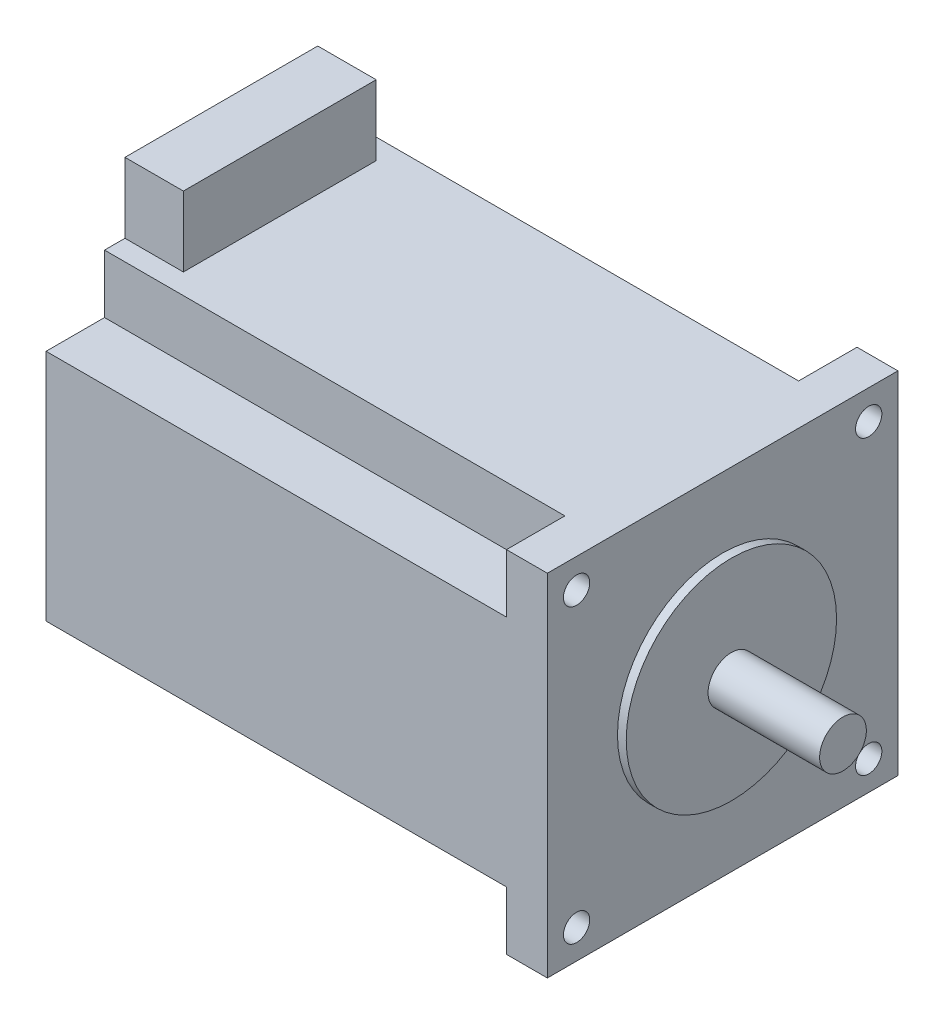
SolidWorks part; units mm, degrees
note: The reader was unsure of these and kept them because the rebuilt part matched: shared geometry of "Sketch1<5>", "Sketch2<2>".
material "7079 Alloy"
ref_plane "Front" through (0, 0, 0) normal (0, 0, 1) x (1, 0, 0)
ref_plane "Top" through (0, 0, 0) normal (0, 1, 0) x (1, 0, 0)
ref_plane "Right" through (0, 0, 0) normal (1, 0, 0) x (0, 0, -1)
sketch "Sketch1" plane through (0, 0, 0) normal (0, 0, 1) x (1, 0, 0)
  line L0 (85.8, 30) -> (106.4, 30)
  line L1 (0, 0) -> (85.8, 0)
  line L2 (0, 0) -> (0, 60)
  line L3 (0, 60) -> (85.8, 60)
  line L4 (85.8, 0) -> (85.8, 60)
  line L5 (85.8, 30) -> (85.8, 48)
  line L6 (85.8, 30) -> (85.8, 12)
  line L7 (85.8, 12) -> (87.3, 12)
  line L8 (87.3, 12) -> (87.3, 48)
  line L9 (87.3, 48) -> (85.8, 48)
  line L10 (106.4, 30) -> (106.4, 34)
  line L11 (106.4, 34) -> (87.3, 34)
  line L12 (106.4, 30) -> (106.4, 26)
  line L13 (106.4, 26) -> (87.3, 26)
  line L14 (106.4, 34) -> (91.4, 34)
  line L15 (91.4, 34) -> (91.4, 26)
  line L16 (0, 60) -> (0, 72)
  line L17 (0, 72) -> (10, 72)
  line L18 (10, 72) -> (10, 60)
  dimension "D1" = 85.8
  dimension "D2" = 60
  dimension "D3" = 10
extrude "Extrude1" add sketch "Sketch1" along normal mid plane 60
extrude "Extrude2" add sketch "Sketch1<5>" along normal mid plane 33 contours L3 L18 L17 L16
sketch "Sketch1<5>" plane through (0, 0, 0) normal (0, 0, 1) x (1, 0, 0) same geometry as "Sketch1"
sketch "Sketch2" plane through (85.8, 0, 0) normal (1, 0, 0) x (0, 0, -1)
  line L0 (0, 30) -> (0, 12) construction
  line L1 (0, 30) -> (0, 48) construction
  circle A0 centre (0, 30) radius 4
  circle A1 centre (0, 30) radius 18
extrude "Extrude3" add sketch "Sketch2" along normal blind 1.5
extrude "Extrude4" add sketch "Sketch2<2>" along normal blind 1.5
sketch "Sketch2<2>" plane through (85.8, 0, 0) normal (1, 0, 0) x (0, 0, -1) same geometry as "Sketch2"
sketch "Sketch4" plane through (85.8, 0, 0) normal (1, 0, 0) x (0, 0, -1)
  line L0 (0, 0) -> (0, 60) construction
  circle A0 centre (0, 30) radius 4
extrude "Extrude5" add sketch "Sketch4" along normal blind 20.6
sketch "Sketch5" plane through (85.8, 0, 0) normal (1, 0, 0) x (0, 0, -1)
  line L0 (0, 30) -> (0, 55)
  line L1 (0, 55) -> (25, 55)
  line L2 (25, 55) -> (25, 5)
  line L3 (25, 5) -> (-25, 5)
  line L4 (-25, 5) -> (-25, 55)
  line L5 (-25, 55) -> (0, 55)
  circle A0 centre (-25, 55) radius 2.25
  circle A1 centre (25, 55) radius 2.25
  circle A2 centre (25, 5) radius 2.25
  circle A3 centre (-25, 5) radius 2.25
extrude "Cut-Extrude1" cut sketch "Sketch5" against normal blind 86 contours A0 | A1 | A3 | A2
sketch "Sketch6" plane through (0, 0, 0) normal (-1, 0, 0) x (0, 0, 1)
  line L1 (-30, 60) -> (-20, 60)
  line L2 (-30, 60) -> (-30, 50)
  line L3 (-30, 50) -> (-20, 50)
  line L4 (-20, 60) -> (-20, 50)
  line L5 (30, 60) -> (20, 60)
  line L6 (30, 60) -> (30, 50)
  line L7 (30, 50) -> (20, 50)
  line L8 (20, 60) -> (20, 50)
  line L9 (-30, 0) -> (-20, 0)
  line L10 (-30, 0) -> (-30, 10)
  line L11 (-30, 10) -> (-20, 10)
  line L12 (-20, 0) -> (-20, 10)
  line L13 (30, 0) -> (20, 0)
  line L14 (30, 0) -> (30, 10)
  line L15 (30, 10) -> (20, 10)
  line L16 (20, 0) -> (20, 10)
  dimension "D1" = 10
  dimension "D2" = 10
  dimension "D3" = 10
  dimension "D4" = 10
  dimension "D5" = 10
  dimension "D6" = 10
  dimension "D7" = 10
  dimension "D8" = 10
extrude "Cut-Extrude2" cut sketch "Sketch6" against normal blind 78.8
